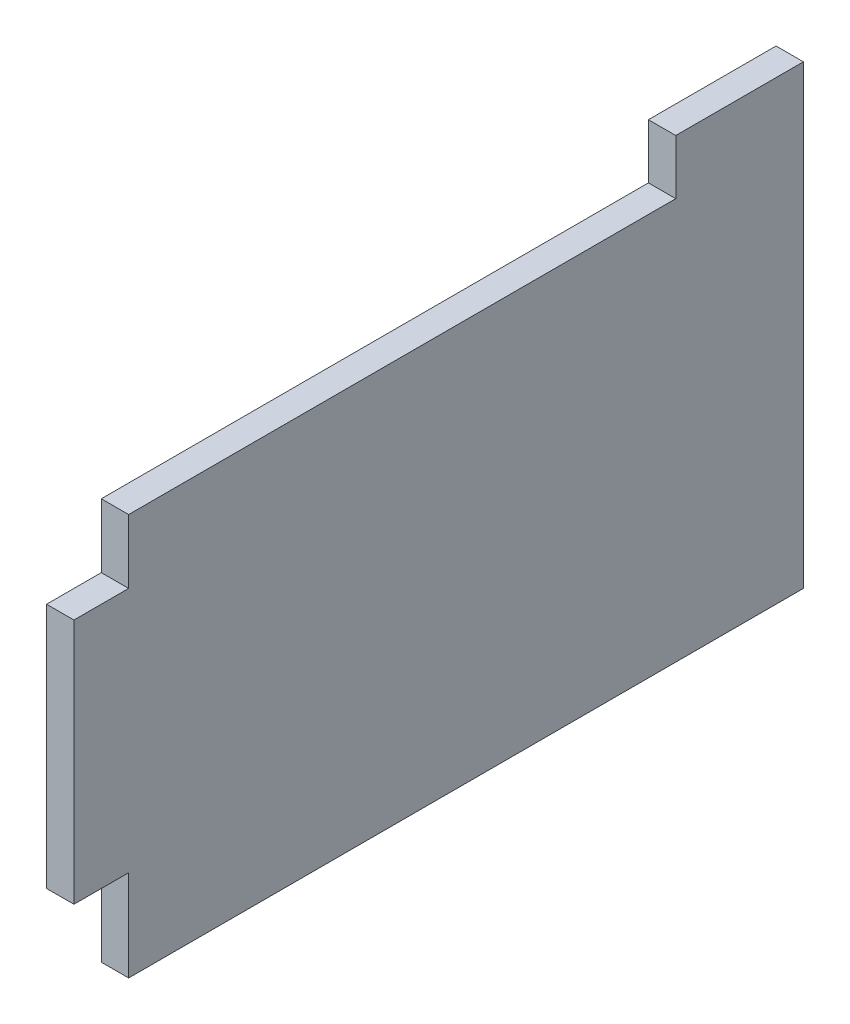
SolidWorks part; units mm, degrees
ref_plane "Front Plane" through (0, 0, 0) normal (0, 0, 1) x (1, 0, 0)
ref_plane "Top Plane" through (0, 0, 0) normal (0, 1, 0) x (1, 0, 0)
ref_plane "Right Plane" through (0, 0, 0) normal (1, 0, 0) x (0, 0, -1)
sketch "Sketch2" plane through (0, 0, 0) normal (1, 0, 0) x (0, 0, -1)
  line L1 (63, 3.0154) -> (103, 3.0154)
  line L3 (3, -47) -> (159.7817, -47)
  line L5 (-3, -10) -> (-3, -37)
  line L10 (3, -2.9846) -> (63, -2.9846)
  line L11 (63, 3.0154) -> (63, -2.9846)
  line L12 (103, 3.0154) -> (103, -2.9846)
  line L13 (165.7817, -10) -> (165.7817, -37)
  line L14 (103, -2.9846) -> (159.7817, -2.9846)
  line L16 (3, -2.9846) -> (3, -10)
  line L17 (-3, -10) -> (3, -10)
  line L18 (-3, -37) -> (3, -37)
  line L19 (3, -37) -> (3, -47)
  line L20 (159.7817, -2.9846) -> (159.7817, -10)
  line L21 (165.7817, -10) -> (159.7817, -10)
  line L22 (165.7817, -37) -> (159.7817, -37)
  line L23 (159.7817, -37) -> (159.7817, -47)
  dimension "D1" = 6
  dimension "D2" = 27
  dimension "D3" = 6
  dimension "D6" = 40
  dimension "D8" = 50.0154
  dimension "D9" = 168.7817
extrude "Boss-Extrude1" add sketch "Sketch2" along normal blind 3
sketch "Sketch3" plane through (0, 0, 0) normal (1, 0, 0) x (0, 0, -1)
  line L0 (77, 4.5941) -> (187.1394, 4.5941)
  line L4 (77, -46.9867) -> (77, 4.5941)
  line L5 (187.1394, 4.5941) -> (187.1394, -56.7775)
  line L6 (187.1394, -56.7775) -> (77, -56.7775)
  line L7 (77, -56.7775) -> (77, -46.9867)
extrude "Cut-Extrude1" cut sketch "Sketch3" along normal blind 10 and the other way blind 10
